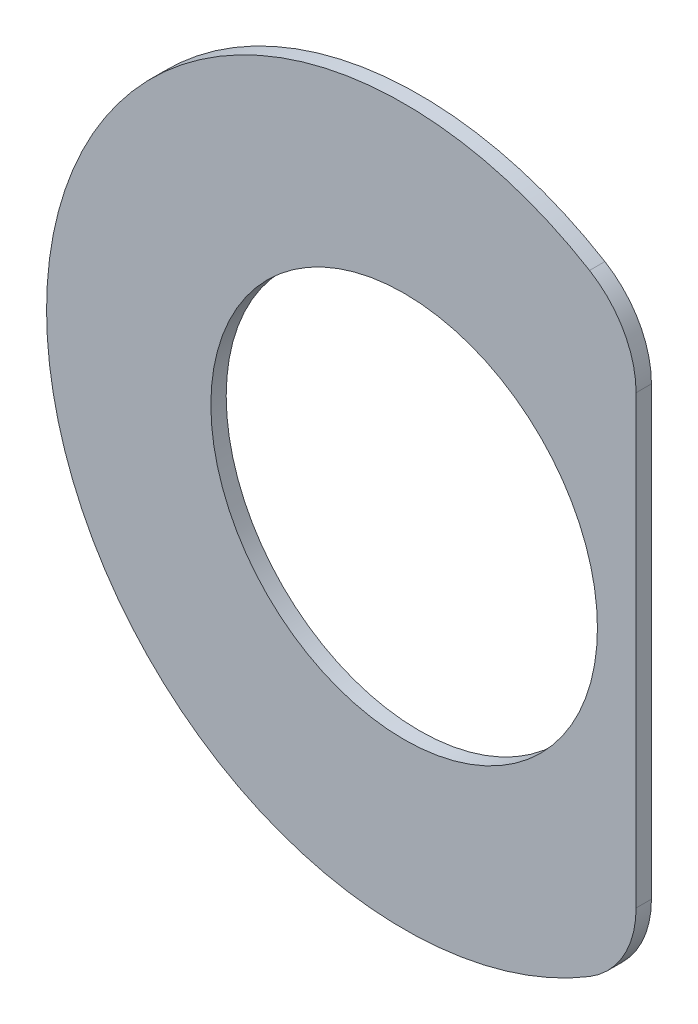
SolidWorks part; units mm, degrees
material "AISI 316 Stainless Steel"
ref_plane "Front Plane" through (0, 0, 0) normal (0, 0, 1) x (1, 0, 0)
ref_plane "Top Plane" through (0, 0, 0) normal (0, 1, 0) x (1, 0, 0)
ref_plane "Right Plane" through (0, 0, 0) normal (1, 0, 0) x (0, 0, -1)
ref_axis "Axis1" through (0, 0, -88.99) along (0, 0, 1)
ref_axis "Axis2" through (0, -55, 0) along (0, 1, 0)
ref_axis "Axis3" through (-88.99, 0, 0) along (1, 0, 0)
sketch "Sketch1" plane through (0, 0, 0) normal (0, 0, 1) x (1, 0, 0)
  line L0 (12, 14.0801) -> (12, -14.0801)
  circle A0 centre (0, 0) radius 10
  circle A1 centre (0, 0) radius 18.5
  dimension "D1" = 20
  dimension "D2" = 37
  dimension "D3" = 2
extrude "Boss-Extrude1" add sketch "Sketch1" along normal blind 0.7937 contours L0 A1 A0 | L0 A1 region at (14.6436, 0, 0) region at (11.5205, 0, 0)
extrude "Cut-Extrude3" cut sketch "Sketch1<3>" along normal through all contours L0 A1 region at (14.6436, 0, 0)
sketch "Sketch1<3>" plane through (0, 0, 0) normal (0, 0, 1) x (1, 0, 0) same geometry as "Sketch1"
fillet "Fillet1" radius 5 2 edges at (12, -14.0801, 0.3969) (12, 14.0801, 0.3969)
